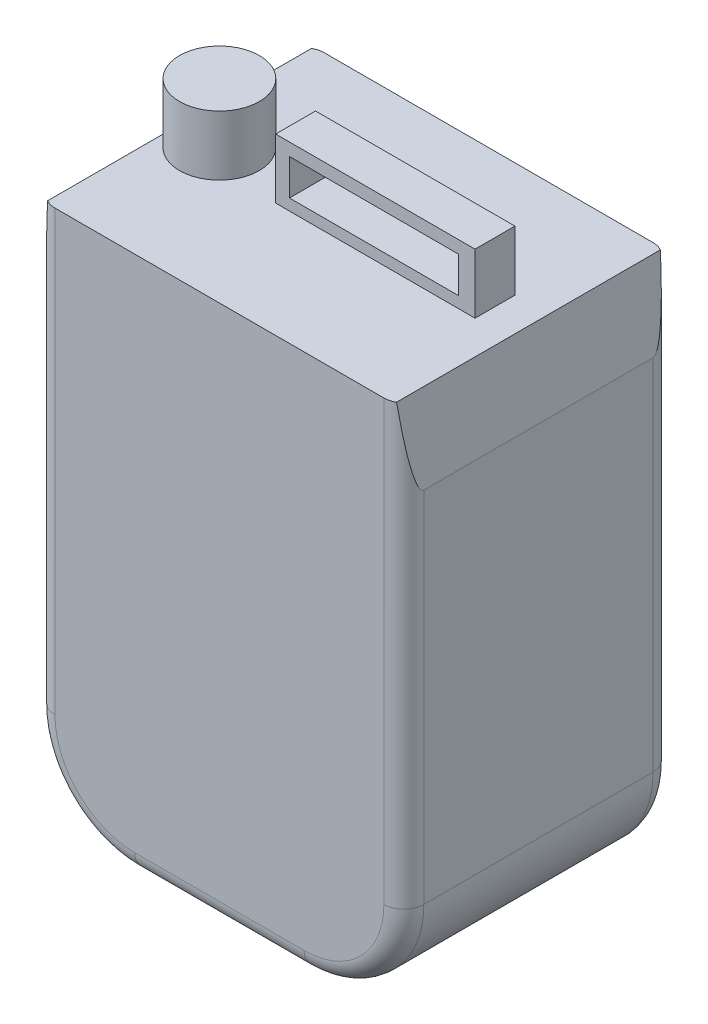
SolidWorks part; units mm, degrees
ref_plane "Front Plane" through (0, 0, 0) normal (0, 0, 1) x (1, 0, 0)
ref_plane "Top Plane" through (0, 0, 0) normal (0, 1, 0) x (1, 0, 0)
ref_plane "Right Plane" through (0, 0, 0) normal (1, 0, 0) x (0, 0, -1)
sketch "Sketch1" plane through (0, 0, 0) normal (0, 0, 1) x (1, 0, 0)
  line L0 (66.0307, -35.6397) -> (66.0307, 504.3603) construction
  line L1 (-21.4693, 234.3603) -> (153.5307, 234.3603)
  line L2 (-26.4693, 194.3603) -> (-26.4693, 14.3603)
  line L3 (23.5307, -35.6397) -> (108.5307, -35.6397)
  line L4 (158.5307, 194.3603) -> (158.5307, 14.3603)
  line L5 (-26.4693, 194.3603) -> (-21.4693, 234.3603)
  line L6 (153.5307, 234.3603) -> (158.5307, 194.3603)
  arc A0 (-26.4693, 14.3603) -> (23.5307, -35.6397) centre (23.5307, 14.3603) ccw
  arc A1 (108.5307, -35.6397) -> (158.5307, 14.3603) centre (108.5307, 14.3603) ccw
  arc A2 (-26.4693, 14.3603) -> (23.5307, -35.6397) centre (23.5307, 14.3603) ccw
  point P15 (66.0307, 234.3603)
  dimension "D1" = 50
  dimension "D2" = 50
extrude "Boss-Extrude2" add sketch "Sketch1" along normal blind 135 contours L2 A2 L3 A1 L4 L6 L1 L5
sketch "Sketch2" plane through (0, 234.3603, 0) normal (0, 1, 0) x (1, 0, 0)
  line L0 (-21.4693, -67.5) -> (186.9159, -67.5) construction
  line L1 (-21.4693, -135) -> (-21.4693, 0) construction
  line L2 (66.0307, 0) -> (66.0307, -136.6082) construction
  line L3 (-21.4693, 0) -> (153.5307, 0) construction
  line L5 (36.7357, -57.5) -> (136.7357, -57.5)
  line L6 (36.7357, -57.5) -> (36.7357, -77.5)
  line L7 (36.7357, -77.5) -> (136.7357, -77.5)
  line L8 (136.7357, -57.5) -> (136.7357, -77.5)
  circle A0 centre (-1.4693, -67.5) radius 20
  point P14 (36.7357, -67.5)
extrude "Boss-Extrude3" add sketch "Sketch2" along normal blind 30
sketch "Sketch3" plane through (0, 0, 77.5) normal (0, 0, 1) x (1, 0, 0)
  line L1 (43.6591, 258.0452) -> (128.5613, 258.0452)
  line L2 (43.6591, 258.0452) -> (43.6591, 240.0303)
  line L3 (43.6591, 240.0303) -> (128.5613, 240.0303)
  line L4 (128.5613, 258.0452) -> (128.5613, 240.0303)
extrude "Cut-Extrude1" cut sketch "Sketch3" against normal blind 30 contours L1 L4 L3 L2
fillet "Fillet1" radius 10 5 edges at (-26.4693, 104.3603, 135) (-11.8246, -20.9951, 135) (66.0307, -35.6397, 135) (143.8861, -20.9951, 135) (158.5307, 104.3603, 135)
fillet "Fillet2" radius 10 5 edges at (-26.4693, 104.3603, 0) (-11.8246, -20.9951, 0) (66.0307, -35.6397, 0) (143.8861, -20.9951, 0) (158.5307, 104.3603, 0)
